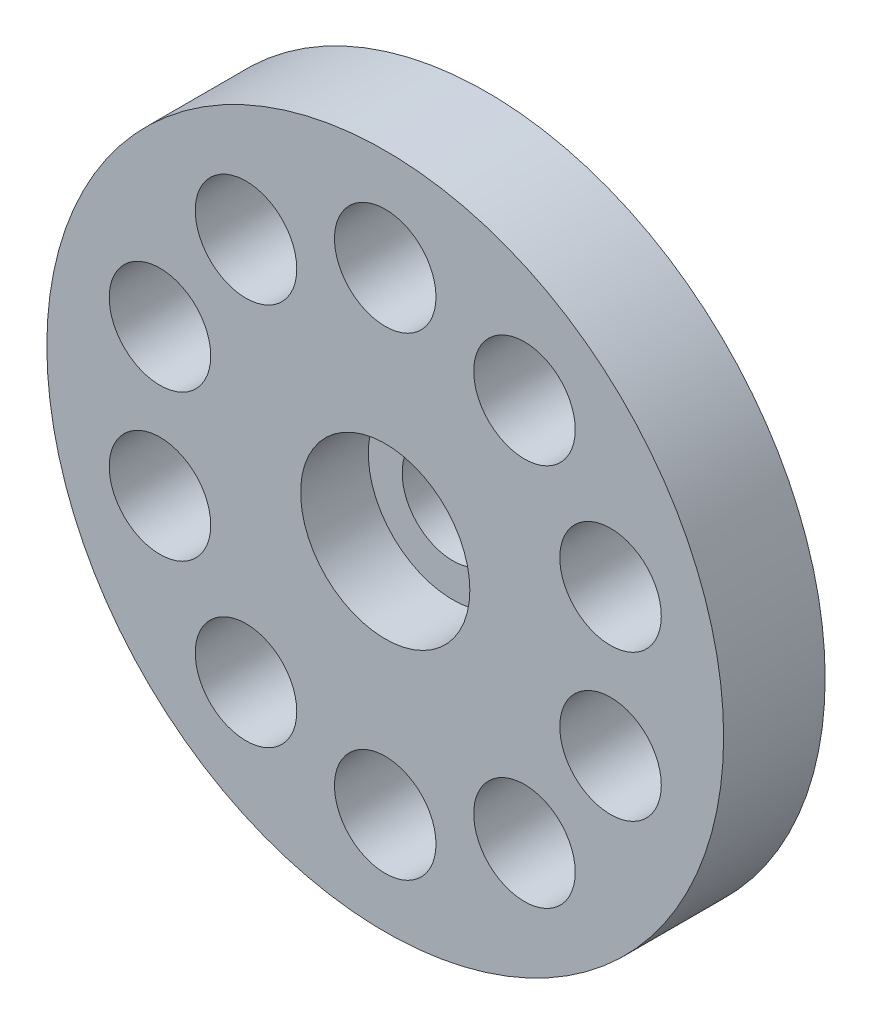
SolidWorks part; units mm, degrees
ref_plane "Front" through (0, 0, 0) normal (0, 0, 1) x (1, 0, 0)
ref_plane "Top" through (0, 0, 0) normal (0, 1, 0) x (1, 0, 0)
ref_plane "Right" through (0, 0, 0) normal (1, 0, 0) x (0, 0, -1)
sketch "Sketch1" plane through (0, 0, 0) normal (0, 0, 1) x (1, 0, 0)
  circle A0 centre (0, 0) radius 10
  circle A1 centre (0, -7) radius 1.5
  circle A3 centre (0, 0) radius 1.5
  circle A4 centre (-4.1145, -5.6631) radius 1.5
  circle A5 centre (-6.6574, -2.1631) radius 1.5
  circle A6 centre (-6.6574, 2.1631) radius 1.5
  circle A7 centre (-4.1145, 5.6631) radius 1.5
  circle A8 centre (0, 7) radius 1.5
  circle A9 centre (4.1145, 5.6631) radius 1.5
  circle A10 centre (6.6574, 2.1631) radius 1.5
  circle A11 centre (6.6574, -2.1631) radius 1.5
  circle A12 centre (4.1145, -5.6631) radius 1.5
  point P28 (0, 0)
  dimension "D2" = 20
  dimension "D3" = 3
  dimension "D4" = 3
  dimension "D1" = 7
  dimension "D7" = 14
  dimension "D6" = 10
extrude "Boss-Extrude1" add sketch "Sketch1" along normal blind 3 contours A0
extrude "Cut-Extrude2" cut sketch "Sketch1<6>" along normal through all contours A3
sketch "Sketch1<6>" plane through (0, 0, 0) normal (0, 0, 1) x (1, 0, 0) same geometry as "Sketch1"
extrude "Cut-Extrude3" cut sketch "Sketch1<7>" along normal through all contours A6 | A5 | A4 | A1 | A12 | A11 | A10 | A9 | A8 | A7
sketch "Sketch1<7>" plane through (0, 0, 0) normal (0, 0, 1) x (1, 0, 0) same geometry as "Sketch1"
ref_plane "Plane1" through (0, 0, 3) normal (0, 0, 1) x (1, 0, 0)
sketch "Sketch3" plane through (0, 0, 3) normal (0, 0, 1) x (1, 0, 0)
  circle A0 centre (0, 0) radius 2.5
  dimension "D1" = 5
extrude "Cut-Extrude5" cut sketch "Sketch3" against normal blind 2
